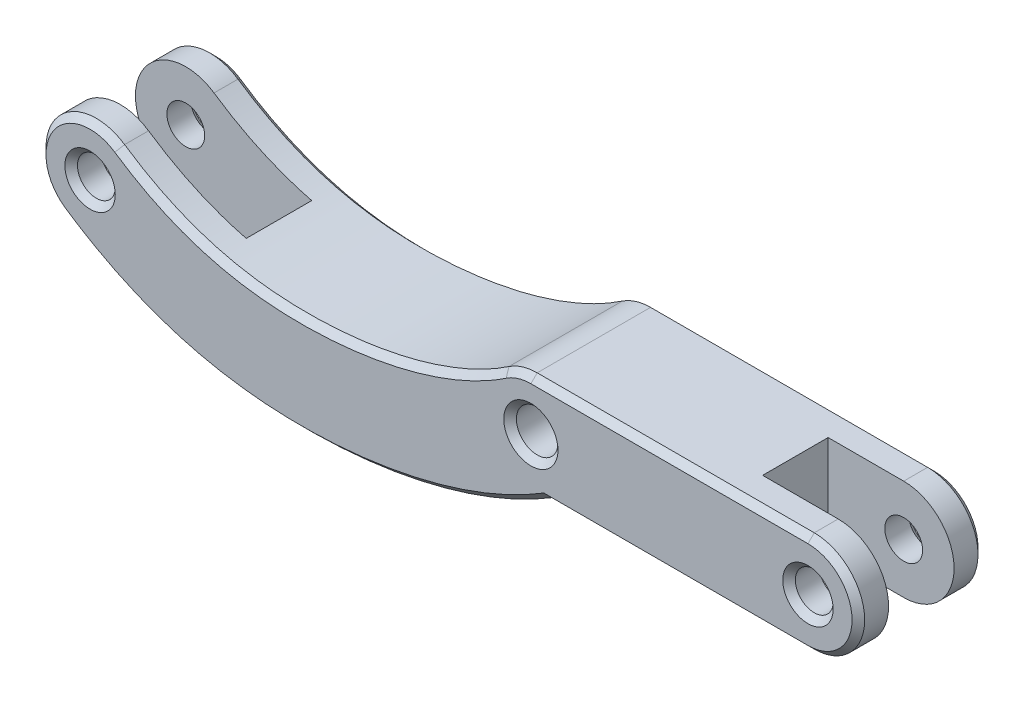
SolidWorks part; units mm, degrees
ref_plane "前视基准面" through (0, 0, 0) normal (0, 0, 1) x (1, 0, 0)
ref_plane "上视基准面" through (0, 0, 0) normal (0, 1, 0) x (1, 0, 0)
ref_plane "右视基准面" through (0, 0, 0) normal (1, 0, 0) x (0, 0, -1)
sketch "草图1" plane through (0, 0, 0) normal (0, 0, 1) x (1, 0, 0)
  line L0 (0, 0) -> (35, 0) construction
  line L1 (-2.2417, -3.3128) -> (17.5, 0) construction
  line L2 (17.5, 0) -> (37.2417, -3.3128) construction
  circle A0 centre (0, 0) radius 4
  circle A1 centre (35, 0) radius 4
  circle A2 centre (0, 0) radius 1.5
  circle A3 centre (35, 0) radius 1.65
  spline S0 degree 3 poles (-2.2417, -3.3128) (4.0233, -7.5521) (17.1379, -10.6929) (31.7009, -7.062) (37.2417, -3.3128) knots 0 0 0 0 0.5 1 1 1 1
  spline S1 degree 1 poles (2.2417, 3.3128) (32.7583, 3.3128) knots 0 0 1 1 construction
  spline S2 degree 3 poles (2.2417, 3.3128) (2.5418, 3.1098) (3.1567, 2.7111) (4.3633, 1.9963) (5.87, 1.2243) (7.6776, 0.4789) (10.1154, -0.2997) (13.2521, -0.9026) (17.3176, -1.0878) (21.6279, -0.7537) (25.8073, 0.1096) (28.9922, 1.2411) (31.2644, 2.3695) (32.2642, 2.9785) (32.7583, 3.3128) knots 0 0 0 0 0.03125 0.0625 0.125 0.1875 0.25 0.375 0.5 0.625 0.75 0.875 0.9375 1 1 1 1
  point P7 (17.5, 0)
  dimension "D1" = 8
  dimension "D5" = 3
  dimension "D6" = 3.3
  dimension "D2" = 35
  dimension "D3" = 9
  dimension "D4" = 8
extrude "凸台-拉伸1" add sketch "草图1" along normal blind 5 and the other way blind 5 contours A0 A2 | A0 S0 A1 | A1 A3 region at (1.8222, -3.4332, 0) region at (17.4648, -4.0639, 0) region at (36.8222, 3.4332, 0)
sketch "草图2" plane through (0, 0, 0) normal (0, 0, 1) x (1, 0, 0)
  circle A0 centre (0, 0) radius 10
  dimension "D1" = 20
extrude "切除-拉伸1" cut sketch "草图2" against normal blind 2.6 and the other way blind 2.6
sketch "草图3" plane through (0, 0, -5) normal (0, 0, -1) x (-1, 0, 0)
  line L0 (-35, 0) -> (-57, 0) construction
  line L1 (-57, 4) -> (-35, 4)
  line L2 (-57, -4) -> (-35, -4)
  arc A0 (-35, -4) -> (-35, 4) centre (-35, 0) ccw
  circle A1 centre (-57, 0) radius 1.5
  arc A2 (-57, 4) -> (-57, -4) centre (-57, 0) ccw
  circle A3 centre (-35, 0) radius 1.65 construction
  circle A4 centre (-35, 0) radius 1.65
  dimension "D2" = 3
  dimension "D1" = 22
extrude "凸台-拉伸3" add sketch "草图3" against normal up to surface (10 mm away) up to face at (1.5, 0, 5)
sketch "草图4" plane through (0, 4, 0) normal (0, 1, 0) x (1, 0, 0)
  line L0 (61, -5) -> (61, 5) construction
  line L1 (51, 2.6) -> (71, 2.6)
  line L2 (51, 2.6) -> (51, -2.6)
  line L3 (51, -2.6) -> (71, -2.6)
  line L4 (71, 2.6) -> (71, -2.6)
  line L5 (51, 2.6) -> (71, -2.6) construction
  line L6 (51, -2.6) -> (71, 2.6) construction
  point P0 (61, 0)
  dimension "D1" = 5.2
  dimension "D2" = 10
extrude "切除-拉伸2" cut sketch "草图4" against normal blind 10
chamfer "倒角1" distance 0.5 angle 45 20 edges at (58.5, 0, 5) (36.65, 0, 5) (1.5, 0, 5) (1.5, 0, -5) (36.65, 0, -5) (55.5, 0, -5) (-3.3128, 2.2417, 5) (46.5859, -4, 5) (33.8277, 3.8244, 5) (61, 0, 5) (46, 4, 5) (46.5859, -4, -5) (61, 0, -5) (46, 4, -5) (-3.3128, 2.2417, -5) (33.8277, 3.8244, -5)
